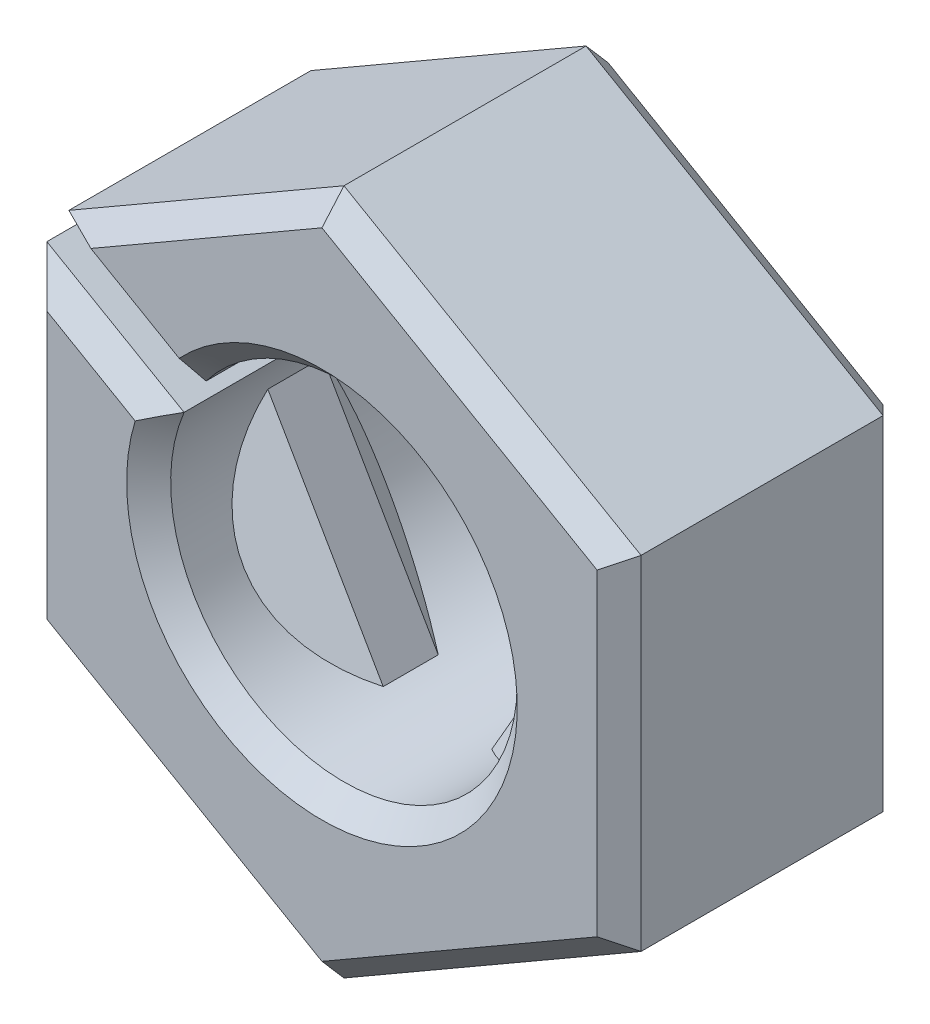
SolidWorks part; units mm, degrees
ref_plane "Front" through (0, 0, 0) normal (0, 0, 1) x (1, 0, 0)
ref_plane "Top" through (0, 0, 0) normal (0, 1, 0) x (1, 0, 0)
ref_plane "Right" through (0, 0, 0) normal (1, 0, 0) x (0, 0, -1)
sketch "Sketch1" plane through (0, 0, 0) normal (0, 0, 1) x (1, 0, 0)
  line L1 (2.7, -1.5588) -> (2.7, 1.5588)
  line L2 (2.7, 1.5588) -> (0, 3.1177)
  line L3 (0, 3.1177) -> (-2.7, 1.5588)
  line L4 (-2.7, 1.5588) -> (-2.7, -1.5588)
  line L5 (-2.7, -1.5588) -> (0, -3.1177)
  line L6 (0, -3.1177) -> (2.7, -1.5588)
  circle A0 centre (0, 0) radius 2.7 construction
  circle A1 centre (0, 0) radius 1.575
  dimension "D1" = 3.15
  dimension "D2" = 5.4
extrude "Boss-Extrude1" add sketch "Sketch1" along normal mid plane 2.6
sketch "Sketch3" plane through (0, 0, 0) normal (1, 0, 0) x (0, 0, -1)
  line L0 (-0.65, 1.575) -> (0.65, 1.575)
  line L1 (1.3, 1.575) -> (-1.3, 1.575) construction
  line L4 (0, 0) -> (0, 1.175) construction
  line L5 (0.65, 1.575) -> (0.25, 1.175)
  line L6 (0.25, 1.175) -> (-0.25, 1.175)
  line L7 (-0.25, 1.175) -> (-0.65, 1.575)
  dimension "D1" = 0.4
  dimension "D2" = 90
  dimension "D3" = 0.5
extrude "Clip" add sketch "Sketch3" along normal up to next and the other way up to next
pattern_circular "Clips x3" count 3 over 360 about axis through (0, 0, 1.3) along (0, 0, 1) of "Clip"
sketch "Sketch4" plane through (0, 0, 0) normal (0, 0, 1) x (1, 0, 0)
  line L0 (-2.7, 1.5588) -> (0, 0)
extrude "Split" cut sketch "Sketch4" against normal through all both and the other way through all thin thin type mid plane wall 0.4
chamfer "Deburs" distance 0.2 angle 45 18 edges at (1.364, -0.7875, -1.3) (2.7, 0, -1.3) (1.35, 2.3383, -1.3) (-1.25, 2.396, -1.3) (-2.7, -0.1155, -1.3) (-1.35, -2.3383, -1.3) (1.35, -2.3383, -1.3) (1.364, -0.7875, 1.3) (-1.35, -2.3383, 1.3) (-2.7, -0.1155, 1.3) (-1.25, 2.396, 1.3) (1.35, 2.3383, 1.3) (2.7, 0, 1.3) (1.35, -2.3383, 1.3) (-1.8765, 1.3143, -1.3) (-2.0765, 0.9679, -1.3) (-1.8765, 1.3143, 1.3) (-2.0765, 0.9679, 1.3)
equation "\"D1@Sketch1\"=\"Clearance Hole Diameter@Box Assy.Assembly\""
equation "\"D2@Sketch1\"=\"Nut Trap Diameter@Box Assy.Assembly\"-0.3mm"
equation "\"D1@Boss-Extrude1\"=\"Nut Trap Depth@Box Assy.Assembly\""
